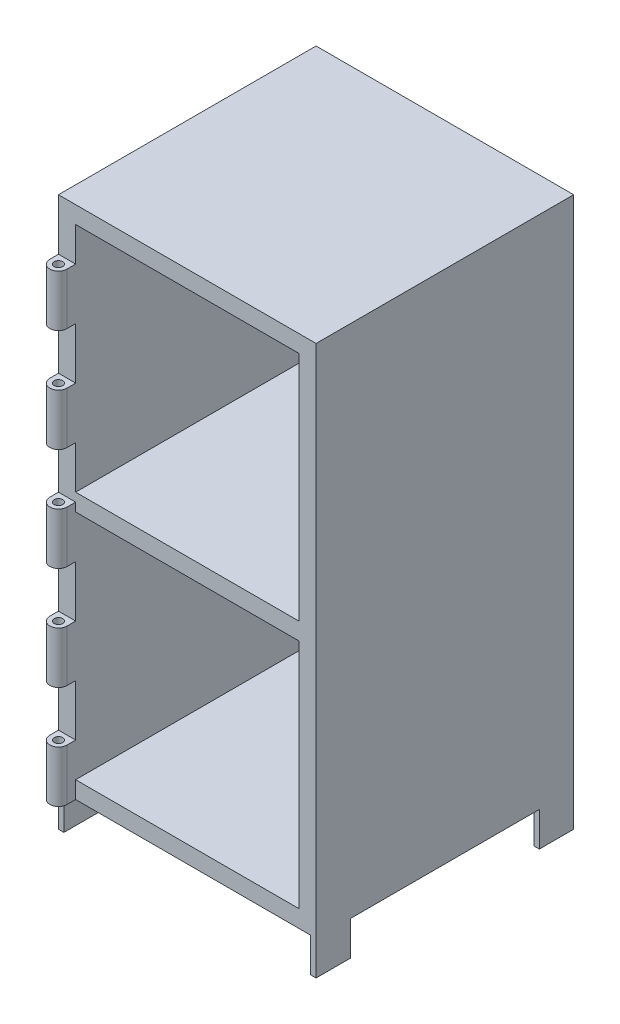
SolidWorks part; units mm, degrees
ref_plane "Front Plane" through (0, 0, 0) normal (0, 0, 1) x (1, 0, 0)
ref_plane "Top Plane" through (0, 0, 0) normal (0, 1, 0) x (1, 0, 0)
ref_plane "Right Plane" through (0, 0, 0) normal (1, 0, 0) x (0, 0, -1)
sketch "Sketch1" plane through (0, 0, 0) normal (0, 1, 0) x (1, 0, 0)
  line L1 (0, 0) -> (150, 0)
  line L2 (0, 0) -> (0, 150)
  line L3 (0, 150) -> (150, 150)
  line L4 (150, 0) -> (150, 150)
  dimension "D1" = 150
  dimension "D2" = 150
extrude "Boss-Extrude1" add sketch "Sketch1" along normal blind 300
sketch "Sketch2" plane through (0, 0, 0) normal (0, 0, 1) x (1, 0, 0)
  line L0 (0, 300) -> (0, 0) construction
  line L1 (10, 145) -> (140, 145)
  line L2 (10, 145) -> (10, 10)
  line L3 (10, 10) -> (140, 10)
  line L4 (140, 145) -> (140, 10)
  line L5 (10, 290) -> (140, 290)
  line L6 (10, 290) -> (10, 155)
  line L7 (10, 155) -> (140, 155)
  line L8 (140, 290) -> (140, 155)
  line L9 (150, 300) -> (150, 0) construction
  line L10 (0, 300) -> (150, 300) construction
  line L11 (0, 0) -> (150, 0) construction
  dimension "D1" = 10
  dimension "D2" = 10
  dimension "D3" = 10
  dimension "D4" = 10
  dimension "D5" = 10
extrude "Cut-Extrude1" cut sketch "Sketch2" against normal blind 130
sketch "Sketch3" plane through (0, 0, 0) normal (-1, 0, 0) x (0, 0, 1)
  line L0 (0, 90) -> (10, 90)
  line L1 (0, 30) -> (10, 30)
  line L2 (0, 30) -> (0, 0)
  line L3 (0, 0) -> (10, 0)
  line L4 (10, 30) -> (10, 0)
  line L5 (0, 90) -> (0, 60)
  line L6 (0, 60) -> (10, 60)
  line L7 (10, 90) -> (10, 60)
  line L8 (0, 150) -> (10, 150)
  line L9 (0, 150) -> (0, 120)
  line L10 (0, 120) -> (10, 120)
  line L11 (10, 150) -> (10, 120)
  line L12 (0, 210) -> (10, 210)
  line L13 (0, 210) -> (0, 180)
  line L14 (0, 180) -> (10, 180)
  line L15 (10, 210) -> (10, 180)
  line L16 (0, 270) -> (10, 270)
  line L17 (0, 270) -> (0, 240)
  line L18 (0, 240) -> (10, 240)
  line L19 (10, 270) -> (10, 240)
  line L20 (0, 30) -> (0, 90) construction
  dimension "D1" = 10
  dimension "D2" = 30
  dimension "D4" = 60
  dimension "D3" = 5
extrude "Boss-Extrude2" add sketch "Sketch3" against normal blind 10
sketch "Sketch4" plane through (0, 270, 0) normal (0, 1, 0) x (1, 0, 0)
  line L0 (0, -10) -> (0, 0) construction
  line L1 (10, -10) -> (0, -10) construction
  circle A0 centre (5, -5) radius 2.5
  dimension "D1" = 5
  dimension "D2" = 5
  dimension "D3" = 5
extrude "Cut-Extrude2" cut sketch "Sketch4" against normal through all
fillet "Fillet1" 2 edges at (0, 255, 10) (10, 255, 10) type full round first side face at (0, 150, -9.0909) second side face at (10, 224.1667, -18.3333) middle face at (5, 255, 10)
fillet "Fillet2" 2 edges at (0, 195, 10) (10, 195, 10) type full round first side face at (0, 150, -9.5455) second side face at (10, 224.1667, -19.1667) middle face at (5, 195, 10)
fillet "Fillet3" 2 edges at (0, 135, 10) (10, 135, 10) type full round first side face at (0, 150, -10) second side face at (10, 75.625, -12.5) middle face at (5, 135, 10)
fillet "Fillet4" 2 edges at (0, 75, 10) (10, 75, 10) type full round first side face at (0, 150, -10.4545) second side face at (10, 75.625, -13.125) middle face at (5, 75, 10)
fillet "Fillet5" 2 edges at (0, 15, 10) (10, 15, 10) type full round first side face at (0, 150, -10.9091) second side face at (10, 75.625, -13.75) middle face at (5, 15, 10)
sketch "Sketch5" plane through (0, 0, 0) normal (0, -1, 0) x (1, 0, 0)
  line L0 (0, -150) -> (0, 5) construction
  line L1 (0, -150) -> (3.175, -150)
  line L2 (0, -150) -> (0, -130)
  line L3 (0, -130) -> (3.175, -130)
  line L4 (3.175, -150) -> (3.175, -130)
  line L5 (150, -150) -> (0, -150) construction
  line L7 (0, 0) -> (3.175, 0)
  line L8 (0, 0) -> (0, -20)
  line L9 (0, -20) -> (3.175, -20)
  line L10 (3.175, 0) -> (3.175, -20)
  line L11 (150, 0) -> (146.825, 0)
  line L12 (150, 0) -> (150, -20)
  line L13 (150, -20) -> (146.825, -20)
  line L14 (146.825, 0) -> (146.825, -20)
  line L15 (150, -150) -> (146.825, -150)
  line L16 (150, -150) -> (150, -130)
  line L17 (150, -130) -> (146.825, -130)
  line L18 (146.825, -150) -> (146.825, -130)
  dimension "D1" = 3.175
  dimension "D2" = 20
extrude "Boss-Extrude3" add sketch "Sketch5" along normal blind 20
